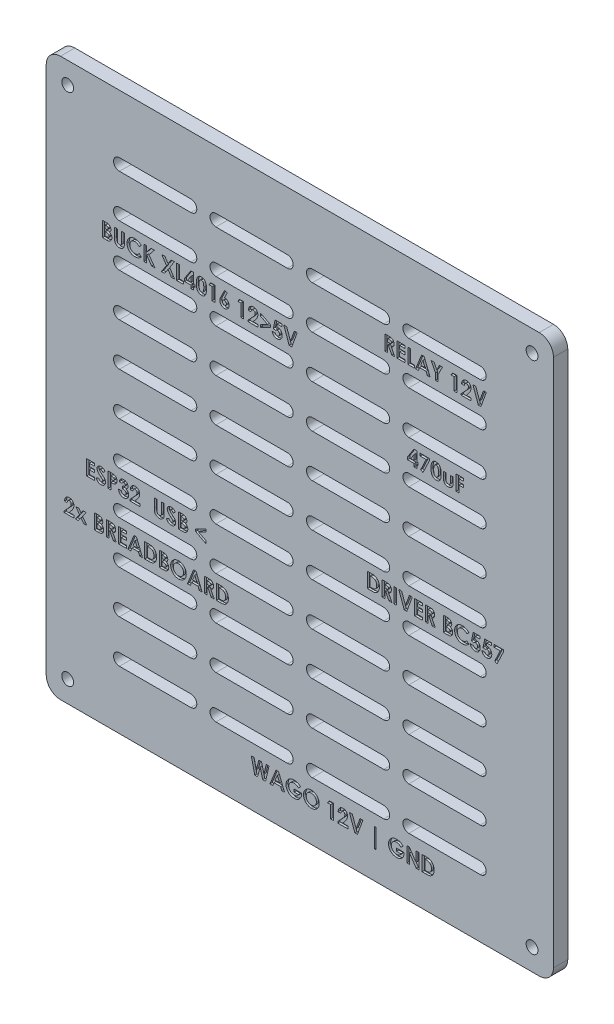
SolidWorks part; units mm, degrees
ref_plane "Front Plane" through (0, 0, 0) normal (0, 0, 1) x (1, 0, 0)
ref_plane "Top Plane" through (0, 0, 0) normal (0, 1, 0) x (1, 0, 0)
ref_plane "Right Plane" through (0, 0, 0) normal (1, 0, 0) x (0, 0, -1)
sketch "Sketch1" plane through (0, 0, 0) normal (0, 0, 1) x (1, 0, 0)
  line L0 (-67, 40) -> (67, 40)
  line L1 (71, 44) -> (71, 192)
  line L2 (67, 196) -> (-67, 196)
  line L3 (-71, 192) -> (-71, 44)
  arc A0 (-71, 44) -> (-67, 40) centre (-67, 44) ccw
  arc A1 (67, 40) -> (71, 44) centre (67, 44) ccw
  arc A2 (71, 192) -> (67, 196) centre (67, 192) ccw
  arc A3 (-67, 196) -> (-71, 192) centre (-67, 192) ccw
extrude "Plate" add sketch "Sketch1" along normal blind 4
sketch "Sketch2" plane through (0, 0, 0) normal (0, 0, 1) x (1, 0, 0)
  line L0 (-50.5, 58) -> (-30.5, 58) construction
  line L1 (-50.5, 59.65) -> (-30.5, 59.65)
  line L2 (-50.5, 56.35) -> (-30.5, 56.35)
  line L3 (-23.5, 58) -> (-3.5, 58) construction
  line L4 (-23.5, 59.65) -> (-3.5, 59.65)
  line L5 (-23.5, 56.35) -> (-3.5, 56.35)
  line L6 (3.5, 58) -> (23.5, 58) construction
  line L7 (3.5, 59.65) -> (23.5, 59.65)
  line L8 (3.5, 56.35) -> (23.5, 56.35)
  line L9 (30.5, 58) -> (50.5, 58) construction
  line L10 (30.5, 59.65) -> (50.5, 59.65)
  line L11 (30.5, 56.35) -> (50.5, 56.35)
  line L12 (-50.5, 70) -> (-30.5, 70) construction
  line L13 (-50.5, 71.65) -> (-30.5, 71.65)
  line L14 (-50.5, 68.35) -> (-30.5, 68.35)
  line L15 (-23.5, 70) -> (-3.5, 70) construction
  line L16 (-23.5, 71.65) -> (-3.5, 71.65)
  line L17 (-23.5, 68.35) -> (-3.5, 68.35)
  line L18 (3.5, 70) -> (23.5, 70) construction
  line L19 (3.5, 71.65) -> (23.5, 71.65)
  line L20 (3.5, 68.35) -> (23.5, 68.35)
  line L21 (30.5, 70) -> (50.5, 70) construction
  line L22 (30.5, 71.65) -> (50.5, 71.65)
  line L23 (30.5, 68.35) -> (50.5, 68.35)
  line L24 (-50.5, 82) -> (-30.5, 82) construction
  line L25 (-50.5, 83.65) -> (-30.5, 83.65)
  line L26 (-50.5, 80.35) -> (-30.5, 80.35)
  line L27 (-23.5, 82) -> (-3.5, 82) construction
  line L28 (-23.5, 83.65) -> (-3.5, 83.65)
  line L29 (-23.5, 80.35) -> (-3.5, 80.35)
  line L30 (3.5, 82) -> (23.5, 82) construction
  line L31 (3.5, 83.65) -> (23.5, 83.65)
  line L32 (3.5, 80.35) -> (23.5, 80.35)
  line L33 (30.5, 82) -> (50.5, 82) construction
  line L34 (30.5, 83.65) -> (50.5, 83.65)
  line L35 (30.5, 80.35) -> (50.5, 80.35)
  line L36 (-50.5, 94) -> (-30.5, 94) construction
  line L37 (-50.5, 95.65) -> (-30.5, 95.65)
  line L38 (-50.5, 92.35) -> (-30.5, 92.35)
  line L39 (-23.5, 94) -> (-3.5, 94) construction
  line L40 (-23.5, 95.65) -> (-3.5, 95.65)
  line L41 (-23.5, 92.35) -> (-3.5, 92.35)
  line L42 (3.5, 94) -> (23.5, 94) construction
  line L43 (3.5, 95.65) -> (23.5, 95.65)
  line L44 (3.5, 92.35) -> (23.5, 92.35)
  line L45 (30.5, 94) -> (50.5, 94) construction
  line L46 (30.5, 95.65) -> (50.5, 95.65)
  line L47 (30.5, 92.35) -> (50.5, 92.35)
  line L48 (-50.5, 106) -> (-30.5, 106) construction
  line L49 (-50.5, 107.65) -> (-30.5, 107.65)
  line L50 (-50.5, 104.35) -> (-30.5, 104.35)
  line L51 (-23.5, 106) -> (-3.5, 106) construction
  line L52 (-23.5, 107.65) -> (-3.5, 107.65)
  line L53 (-23.5, 104.35) -> (-3.5, 104.35)
  line L54 (3.5, 106) -> (23.5, 106) construction
  line L55 (3.5, 107.65) -> (23.5, 107.65)
  line L56 (3.5, 104.35) -> (23.5, 104.35)
  line L57 (30.5, 106) -> (50.5, 106) construction
  line L58 (30.5, 107.65) -> (50.5, 107.65)
  line L59 (30.5, 104.35) -> (50.5, 104.35)
  line L60 (-50.5, 118) -> (-30.5, 118) construction
  line L61 (-50.5, 119.65) -> (-30.5, 119.65)
  line L62 (-50.5, 116.35) -> (-30.5, 116.35)
  line L63 (-23.5, 118) -> (-3.5, 118) construction
  line L64 (-23.5, 119.65) -> (-3.5, 119.65)
  line L65 (-23.5, 116.35) -> (-3.5, 116.35)
  line L66 (3.5, 118) -> (23.5, 118) construction
  line L67 (3.5, 119.65) -> (23.5, 119.65)
  line L68 (3.5, 116.35) -> (23.5, 116.35)
  line L69 (30.5, 118) -> (50.5, 118) construction
  line L70 (30.5, 119.65) -> (50.5, 119.65)
  line L71 (30.5, 116.35) -> (50.5, 116.35)
  line L72 (-50.5, 130) -> (-30.5, 130) construction
  line L73 (-50.5, 131.65) -> (-30.5, 131.65)
  line L74 (-50.5, 128.35) -> (-30.5, 128.35)
  line L75 (-23.5, 130) -> (-3.5, 130) construction
  line L76 (-23.5, 131.65) -> (-3.5, 131.65)
  line L77 (-23.5, 128.35) -> (-3.5, 128.35)
  line L78 (3.5, 130) -> (23.5, 130) construction
  line L79 (3.5, 131.65) -> (23.5, 131.65)
  line L80 (3.5, 128.35) -> (23.5, 128.35)
  line L81 (30.5, 130) -> (50.5, 130) construction
  line L82 (30.5, 131.65) -> (50.5, 131.65)
  line L83 (30.5, 128.35) -> (50.5, 128.35)
  line L84 (-50.5, 142) -> (-30.5, 142) construction
  line L85 (-50.5, 143.65) -> (-30.5, 143.65)
  line L86 (-50.5, 140.35) -> (-30.5, 140.35)
  line L87 (-23.5, 142) -> (-3.5, 142) construction
  line L88 (-23.5, 143.65) -> (-3.5, 143.65)
  line L89 (-23.5, 140.35) -> (-3.5, 140.35)
  line L90 (3.5, 142) -> (23.5, 142) construction
  line L91 (3.5, 143.65) -> (23.5, 143.65)
  line L92 (3.5, 140.35) -> (23.5, 140.35)
  line L93 (30.5, 142) -> (50.5, 142) construction
  line L94 (30.5, 143.65) -> (50.5, 143.65)
  line L95 (30.5, 140.35) -> (50.5, 140.35)
  line L96 (-50.5, 154) -> (-30.5, 154) construction
  line L97 (-50.5, 155.65) -> (-30.5, 155.65)
  line L98 (-50.5, 152.35) -> (-30.5, 152.35)
  line L99 (-23.5, 154) -> (-3.5, 154) construction
  line L100 (-23.5, 155.65) -> (-3.5, 155.65)
  line L101 (-23.5, 152.35) -> (-3.5, 152.35)
  line L102 (3.5, 154) -> (23.5, 154) construction
  line L103 (3.5, 155.65) -> (23.5, 155.65)
  line L104 (3.5, 152.35) -> (23.5, 152.35)
  line L105 (30.5, 154) -> (50.5, 154) construction
  line L106 (30.5, 155.65) -> (50.5, 155.65)
  line L107 (30.5, 152.35) -> (50.5, 152.35)
  line L108 (-50.5, 166) -> (-30.5, 166) construction
  line L109 (-50.5, 167.65) -> (-30.5, 167.65)
  line L110 (-50.5, 164.35) -> (-30.5, 164.35)
  line L111 (-23.5, 166) -> (-3.5, 166) construction
  line L112 (-23.5, 167.65) -> (-3.5, 167.65)
  line L113 (-23.5, 164.35) -> (-3.5, 164.35)
  line L114 (3.5, 166) -> (23.5, 166) construction
  line L115 (3.5, 167.65) -> (23.5, 167.65)
  line L116 (3.5, 164.35) -> (23.5, 164.35)
  line L117 (30.5, 166) -> (50.5, 166) construction
  line L118 (30.5, 167.65) -> (50.5, 167.65)
  line L119 (30.5, 164.35) -> (50.5, 164.35)
  line L120 (-50.5, 178) -> (-30.5, 178) construction
  line L121 (-50.5, 179.65) -> (-30.5, 179.65)
  line L122 (-50.5, 176.35) -> (-30.5, 176.35)
  line L123 (-23.5, 178) -> (-3.5, 178) construction
  line L124 (-23.5, 179.65) -> (-3.5, 179.65)
  line L125 (-23.5, 176.35) -> (-3.5, 176.35)
  line L126 (3.5, 178) -> (23.5, 178) construction
  line L127 (3.5, 179.65) -> (23.5, 179.65)
  line L128 (3.5, 176.35) -> (23.5, 176.35)
  line L129 (30.5, 178) -> (50.5, 178) construction
  line L130 (30.5, 179.65) -> (50.5, 179.65)
  line L131 (30.5, 176.35) -> (50.5, 176.35)
  circle A0 centre (-65, 46) radius 1.65
  circle A1 centre (65, 46) radius 1.65
  circle A2 centre (-65, 190) radius 1.65
  circle A3 centre (65, 190) radius 1.65
  arc A4 (-50.5, 59.65) -> (-50.5, 56.35) centre (-50.5, 58) ccw
  arc A5 (-30.5, 56.35) -> (-30.5, 59.65) centre (-30.5, 58) ccw
  arc A6 (-23.5, 59.65) -> (-23.5, 56.35) centre (-23.5, 58) ccw
  arc A7 (-3.5, 56.35) -> (-3.5, 59.65) centre (-3.5, 58) ccw
  arc A8 (3.5, 59.65) -> (3.5, 56.35) centre (3.5, 58) ccw
  arc A9 (23.5, 56.35) -> (23.5, 59.65) centre (23.5, 58) ccw
  arc A10 (30.5, 59.65) -> (30.5, 56.35) centre (30.5, 58) ccw
  arc A11 (50.5, 56.35) -> (50.5, 59.65) centre (50.5, 58) ccw
  arc A12 (-50.5, 71.65) -> (-50.5, 68.35) centre (-50.5, 70) ccw
  arc A13 (-30.5, 68.35) -> (-30.5, 71.65) centre (-30.5, 70) ccw
  arc A14 (-23.5, 71.65) -> (-23.5, 68.35) centre (-23.5, 70) ccw
  arc A15 (-3.5, 68.35) -> (-3.5, 71.65) centre (-3.5, 70) ccw
  arc A16 (3.5, 71.65) -> (3.5, 68.35) centre (3.5, 70) ccw
  arc A17 (23.5, 68.35) -> (23.5, 71.65) centre (23.5, 70) ccw
  arc A18 (30.5, 71.65) -> (30.5, 68.35) centre (30.5, 70) ccw
  arc A19 (50.5, 68.35) -> (50.5, 71.65) centre (50.5, 70) ccw
  arc A20 (-50.5, 83.65) -> (-50.5, 80.35) centre (-50.5, 82) ccw
  arc A21 (-30.5, 80.35) -> (-30.5, 83.65) centre (-30.5, 82) ccw
  arc A22 (-23.5, 83.65) -> (-23.5, 80.35) centre (-23.5, 82) ccw
  arc A23 (-3.5, 80.35) -> (-3.5, 83.65) centre (-3.5, 82) ccw
  arc A24 (3.5, 83.65) -> (3.5, 80.35) centre (3.5, 82) ccw
  arc A25 (23.5, 80.35) -> (23.5, 83.65) centre (23.5, 82) ccw
  arc A26 (30.5, 83.65) -> (30.5, 80.35) centre (30.5, 82) ccw
  arc A27 (50.5, 80.35) -> (50.5, 83.65) centre (50.5, 82) ccw
  arc A28 (-50.5, 95.65) -> (-50.5, 92.35) centre (-50.5, 94) ccw
  arc A29 (-30.5, 92.35) -> (-30.5, 95.65) centre (-30.5, 94) ccw
  arc A30 (-23.5, 95.65) -> (-23.5, 92.35) centre (-23.5, 94) ccw
  arc A31 (-3.5, 92.35) -> (-3.5, 95.65) centre (-3.5, 94) ccw
  arc A32 (3.5, 95.65) -> (3.5, 92.35) centre (3.5, 94) ccw
  arc A33 (23.5, 92.35) -> (23.5, 95.65) centre (23.5, 94) ccw
  arc A34 (30.5, 95.65) -> (30.5, 92.35) centre (30.5, 94) ccw
  arc A35 (50.5, 92.35) -> (50.5, 95.65) centre (50.5, 94) ccw
  arc A36 (-50.5, 107.65) -> (-50.5, 104.35) centre (-50.5, 106) ccw
  arc A37 (-30.5, 104.35) -> (-30.5, 107.65) centre (-30.5, 106) ccw
  arc A38 (-23.5, 107.65) -> (-23.5, 104.35) centre (-23.5, 106) ccw
  arc A39 (-3.5, 104.35) -> (-3.5, 107.65) centre (-3.5, 106) ccw
  arc A40 (3.5, 107.65) -> (3.5, 104.35) centre (3.5, 106) ccw
  arc A41 (23.5, 104.35) -> (23.5, 107.65) centre (23.5, 106) ccw
  arc A42 (30.5, 107.65) -> (30.5, 104.35) centre (30.5, 106) ccw
  arc A43 (50.5, 104.35) -> (50.5, 107.65) centre (50.5, 106) ccw
  arc A44 (-50.5, 119.65) -> (-50.5, 116.35) centre (-50.5, 118) ccw
  arc A45 (-30.5, 116.35) -> (-30.5, 119.65) centre (-30.5, 118) ccw
  arc A46 (-23.5, 119.65) -> (-23.5, 116.35) centre (-23.5, 118) ccw
  arc A47 (-3.5, 116.35) -> (-3.5, 119.65) centre (-3.5, 118) ccw
  arc A48 (3.5, 119.65) -> (3.5, 116.35) centre (3.5, 118) ccw
  arc A49 (23.5, 116.35) -> (23.5, 119.65) centre (23.5, 118) ccw
  arc A50 (30.5, 119.65) -> (30.5, 116.35) centre (30.5, 118) ccw
  arc A51 (50.5, 116.35) -> (50.5, 119.65) centre (50.5, 118) ccw
  arc A52 (-50.5, 131.65) -> (-50.5, 128.35) centre (-50.5, 130) ccw
  arc A53 (-30.5, 128.35) -> (-30.5, 131.65) centre (-30.5, 130) ccw
  arc A54 (-23.5, 131.65) -> (-23.5, 128.35) centre (-23.5, 130) ccw
  arc A55 (-3.5, 128.35) -> (-3.5, 131.65) centre (-3.5, 130) ccw
  arc A56 (3.5, 131.65) -> (3.5, 128.35) centre (3.5, 130) ccw
  arc A57 (23.5, 128.35) -> (23.5, 131.65) centre (23.5, 130) ccw
  arc A58 (30.5, 131.65) -> (30.5, 128.35) centre (30.5, 130) ccw
  arc A59 (50.5, 128.35) -> (50.5, 131.65) centre (50.5, 130) ccw
  arc A60 (-50.5, 143.65) -> (-50.5, 140.35) centre (-50.5, 142) ccw
  arc A61 (-30.5, 140.35) -> (-30.5, 143.65) centre (-30.5, 142) ccw
  arc A62 (-23.5, 143.65) -> (-23.5, 140.35) centre (-23.5, 142) ccw
  arc A63 (-3.5, 140.35) -> (-3.5, 143.65) centre (-3.5, 142) ccw
  arc A64 (3.5, 143.65) -> (3.5, 140.35) centre (3.5, 142) ccw
  arc A65 (23.5, 140.35) -> (23.5, 143.65) centre (23.5, 142) ccw
  arc A66 (30.5, 143.65) -> (30.5, 140.35) centre (30.5, 142) ccw
  arc A67 (50.5, 140.35) -> (50.5, 143.65) centre (50.5, 142) ccw
  arc A68 (-50.5, 155.65) -> (-50.5, 152.35) centre (-50.5, 154) ccw
  arc A69 (-30.5, 152.35) -> (-30.5, 155.65) centre (-30.5, 154) ccw
  arc A70 (-23.5, 155.65) -> (-23.5, 152.35) centre (-23.5, 154) ccw
  arc A71 (-3.5, 152.35) -> (-3.5, 155.65) centre (-3.5, 154) ccw
  arc A72 (3.5, 155.65) -> (3.5, 152.35) centre (3.5, 154) ccw
  arc A73 (23.5, 152.35) -> (23.5, 155.65) centre (23.5, 154) ccw
  arc A74 (30.5, 155.65) -> (30.5, 152.35) centre (30.5, 154) ccw
  arc A75 (50.5, 152.35) -> (50.5, 155.65) centre (50.5, 154) ccw
  arc A76 (-50.5, 167.65) -> (-50.5, 164.35) centre (-50.5, 166) ccw
  arc A77 (-30.5, 164.35) -> (-30.5, 167.65) centre (-30.5, 166) ccw
  arc A78 (-23.5, 167.65) -> (-23.5, 164.35) centre (-23.5, 166) ccw
  arc A79 (-3.5, 164.35) -> (-3.5, 167.65) centre (-3.5, 166) ccw
  arc A80 (3.5, 167.65) -> (3.5, 164.35) centre (3.5, 166) ccw
  arc A81 (23.5, 164.35) -> (23.5, 167.65) centre (23.5, 166) ccw
  arc A82 (30.5, 167.65) -> (30.5, 164.35) centre (30.5, 166) ccw
  arc A83 (50.5, 164.35) -> (50.5, 167.65) centre (50.5, 166) ccw
  arc A84 (-50.5, 179.65) -> (-50.5, 176.35) centre (-50.5, 178) ccw
  arc A85 (-30.5, 176.35) -> (-30.5, 179.65) centre (-30.5, 178) ccw
  arc A86 (-23.5, 179.65) -> (-23.5, 176.35) centre (-23.5, 178) ccw
  arc A87 (-3.5, 176.35) -> (-3.5, 179.65) centre (-3.5, 178) ccw
  arc A88 (3.5, 179.65) -> (3.5, 176.35) centre (3.5, 178) ccw
  arc A89 (23.5, 176.35) -> (23.5, 179.65) centre (23.5, 178) ccw
  arc A90 (30.5, 179.65) -> (30.5, 176.35) centre (30.5, 178) ccw
  arc A91 (50.5, 176.35) -> (50.5, 179.65) centre (50.5, 178) ccw
  point P10 (-40.5, 58)
  point P15 (-13.5, 58)
  point P22 (13.5, 58)
  point P29 (40.5, 58)
  point P36 (-40.5, 70)
  point P43 (-13.5, 70)
  point P50 (13.5, 70)
  point P57 (40.5, 70)
  point P64 (-40.5, 82)
  point P71 (-13.5, 82)
  point P78 (13.5, 82)
  point P85 (40.5, 82)
  point P92 (-40.5, 94)
  point P99 (-13.5, 94)
  point P106 (13.5, 94)
  point P113 (40.5, 94)
  point P120 (-40.5, 106)
  point P127 (-13.5, 106)
  point P134 (13.5, 106)
  point P141 (40.5, 106)
  point P148 (-40.5, 118)
  point P155 (-13.5, 118)
  point P162 (13.5, 118)
  point P169 (40.5, 118)
  point P176 (-40.5, 130)
  point P183 (-13.5, 130)
  point P190 (13.5, 130)
  point P197 (40.5, 130)
  point P204 (-40.5, 142)
  point P211 (-13.5, 142)
  point P218 (13.5, 142)
  point P225 (40.5, 142)
  point P232 (-40.5, 154)
  point P239 (-13.5, 154)
  point P246 (13.5, 154)
  point P253 (40.5, 154)
  point P260 (-40.5, 166)
  point P267 (-13.5, 166)
  point P274 (13.5, 166)
  point P281 (40.5, 166)
  point P288 (-40.5, 178)
  point P295 (-13.5, 178)
  point P302 (13.5, 178)
  point P309 (40.5, 178)
extrude "Mounting slots" cut sketch "Sketch2" along normal through all
ref_plane "P1_Front_4" through (0, 0, 4) normal (0, 0, 1) x (1, 0, 0)
sketch "Sketch3" plane through (0, 0, 4) normal (0, 0, 1) x (1, 0, 0)
  text T0 "BUCK XL4016 12>5V" font "Century Gothic" height 4.2
  text T1 "RELAY 12V" font "Century Gothic" height 4.2
  text T2 "470uF" font "Century Gothic" height 4.2
  text T3 "ESP32  USB <" font "Century Gothic" height 4.2
  text T4 "2x BREADBOARD" font "Century Gothic" height 4.2
  text T5 "DRIVER BC557" font "Century Gothic" height 4.2
  text T6 "WAGO 12V | GND" font "Century Gothic" height 4.2
extrude "Zone labels" cut sketch "Sketch3" against normal blind 0.6
